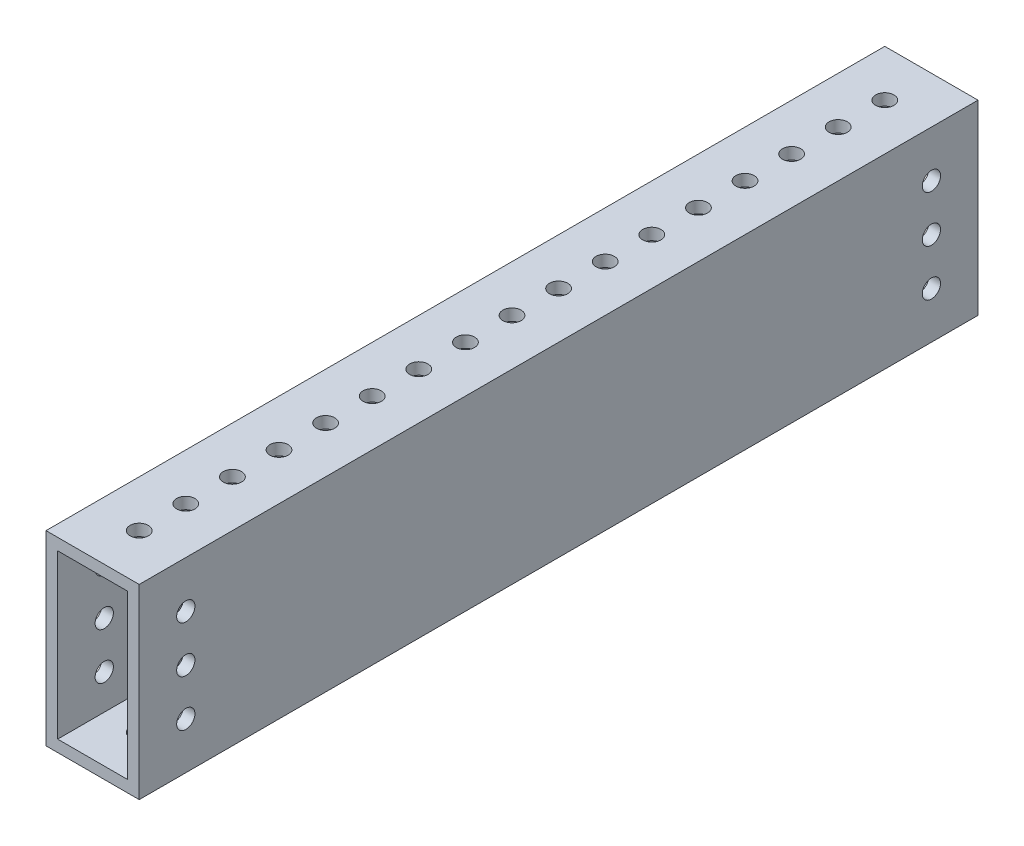
SolidWorks part; units mm, degrees
material "6061-T6 (SS)"
ref_plane "Front Plane" through (0, 0, 0) normal (0, 0, 1) x (1, 0, 0)
ref_plane "Top Plane" through (0, 0, 0) normal (0, 1, 0) x (1, 0, 0)
ref_plane "Right Plane" through (0, 0, 0) normal (1, 0, 0) x (0, 0, -1)
sketch "Sketch1" plane through (0, 0, 0) normal (0, 0, 1) x (1, 0, 0)
  line L0 (-9.525, 22.225) -> (9.525, 22.225)
  line L1 (-12.7, 25.4) -> (12.7, 25.4)
  line L2 (-12.7, 25.4) -> (-12.7, -25.4)
  line L3 (-12.7, -25.4) -> (12.7, -25.4)
  line L4 (12.7, 25.4) -> (12.7, -25.4)
  line L5 (9.525, 22.225) -> (9.525, -22.225)
  line L6 (-9.525, -22.225) -> (9.525, -22.225)
  line L7 (-9.525, 22.225) -> (-9.525, -22.225)
  line L8 (-12.7, 25.4) -> (12.7, -25.4) construction
  line L9 (12.7, 25.4) -> (-12.7, -25.4) construction
  point P5 (0, 0)
  dimension "D1" = 25.4
  dimension "D2" = 50.8
  dimension "D3" = 3.175
extrude "Boss-Extrude1" add sketch "Sketch1" along normal mid plane 228.6
sketch "Sketch2" plane through (0, 25.4, 0) normal (0, 1, 0) x (1, 0, 0)
  line L4 (12.7, -114.3) -> (-12.7, -114.3) construction
  circle A64 centre (0, -101.6) radius 2.4892
  circle A65 centre (0, -88.9) radius 2.4892
  circle A66 centre (0, -76.2) radius 2.4892
  circle A67 centre (0, -63.5) radius 2.4892
  circle A68 centre (0, -50.8) radius 2.4892
  circle A69 centre (0, -38.1) radius 2.4892
  circle A70 centre (0, -25.4) radius 2.4892
  circle A71 centre (0, -12.7) radius 2.4892
  circle A72 centre (0, 0) radius 2.4892
  circle A73 centre (0, 12.7) radius 2.4892
  circle A74 centre (0, 25.4) radius 2.4892
  circle A75 centre (0, 38.1) radius 2.4892
  circle A76 centre (0, 50.8) radius 2.4892
  circle A77 centre (0, 63.5) radius 2.4892
  circle A78 centre (0, 76.2) radius 2.4892
  circle A79 centre (0, 88.9) radius 2.4892
  circle A80 centre (0, 101.6) radius 2.4892
  circle A82 centre (0, 114.3) radius 2.4892 [skipped]
  dimension "D2" = 12.7
  dimension "D4" = 12.7
  dimension "D1" = 4.9784
  dimension "D3" = 18
extrude "Cut-Extrude1" cut sketch "Sketch2" against normal through all
sketch "Sketch3" plane through (-12.7, 0, 0) normal (-1, 0, 0) x (0, 0, 1)
  line L0 (101.6, -25.4) -> (101.6, 25.4) construction
  line L1 (114.3, -25.4) -> (-114.3, -25.4) construction
  line L2 (114.3, 25.4) -> (-114.3, 25.4) construction
  line L3 (114.3, 25.4) -> (114.3, -25.4) construction
  circle A0 centre (101.6, 0) radius 2.4892
  circle A1 centre (101.6, -12.7) radius 2.4892
  circle A2 centre (101.6, 12.7) radius 2.4892
  dimension "D2" = 4.9784
  dimension "D4" = 12.7
  dimension "D1" = 12.7
  dimension "D3" = 12.7
extrude "Cut-Extrude2" cut sketch "Sketch3" against normal through all
mirror "Mirror1" about plane through (0, 0, 0) normal (0, 0, 1) of "Cut-Extrude2"
